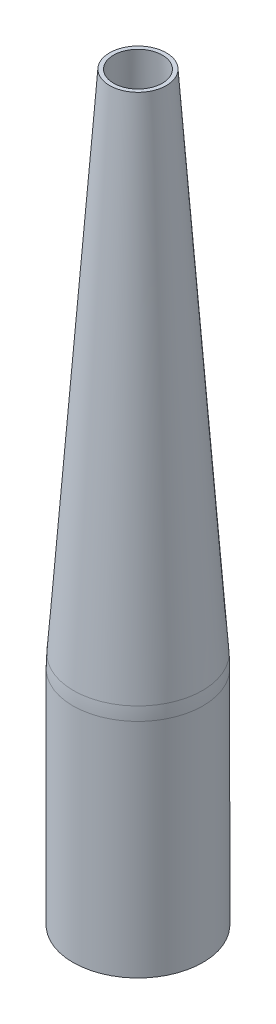
SolidWorks part; units mm, degrees
ref_plane "Front Plane" through (0, 0, 0) normal (0, 0, 1) x (1, 0, 0)
ref_plane "Top Plane" through (0, 0, 0) normal (0, 1, 0) x (1, 0, 0)
ref_plane "Right Plane" through (0, 0, 0) normal (1, 0, 0) x (0, 0, -1)
sketch "Sketch1" plane through (0, 0, 0) normal (0, 0, 1) x (1, 0, 0)
  line L0 (0, 0) -> (27.051, 0)
  line L1 (27.051, 0) -> (27.051, 95.25)
  line L2 (27.051, 95.25) -> (0, 473.964)
  line L3 (0, 473.964) -> (0, 0)
  line L4 (0, 308.61) -> (11.811, 308.61)
  dimension "D1" = 95.25
  dimension "D2" = 378.714
  dimension "D3" = 27.051
  dimension "D4" = 11.811
revolve "Revolve1" add sketch "Sketch1" angle 360 about L3 region at (11.483, 134.1868, 0)
shell "Shell1" thickness 1.651 removed face at (0, 308.61, 11.811) removed face at (0, 0, 27.051)
fillet "Fillet1" radius 76.2 1 edges at (0, 95.25, 27.051)
